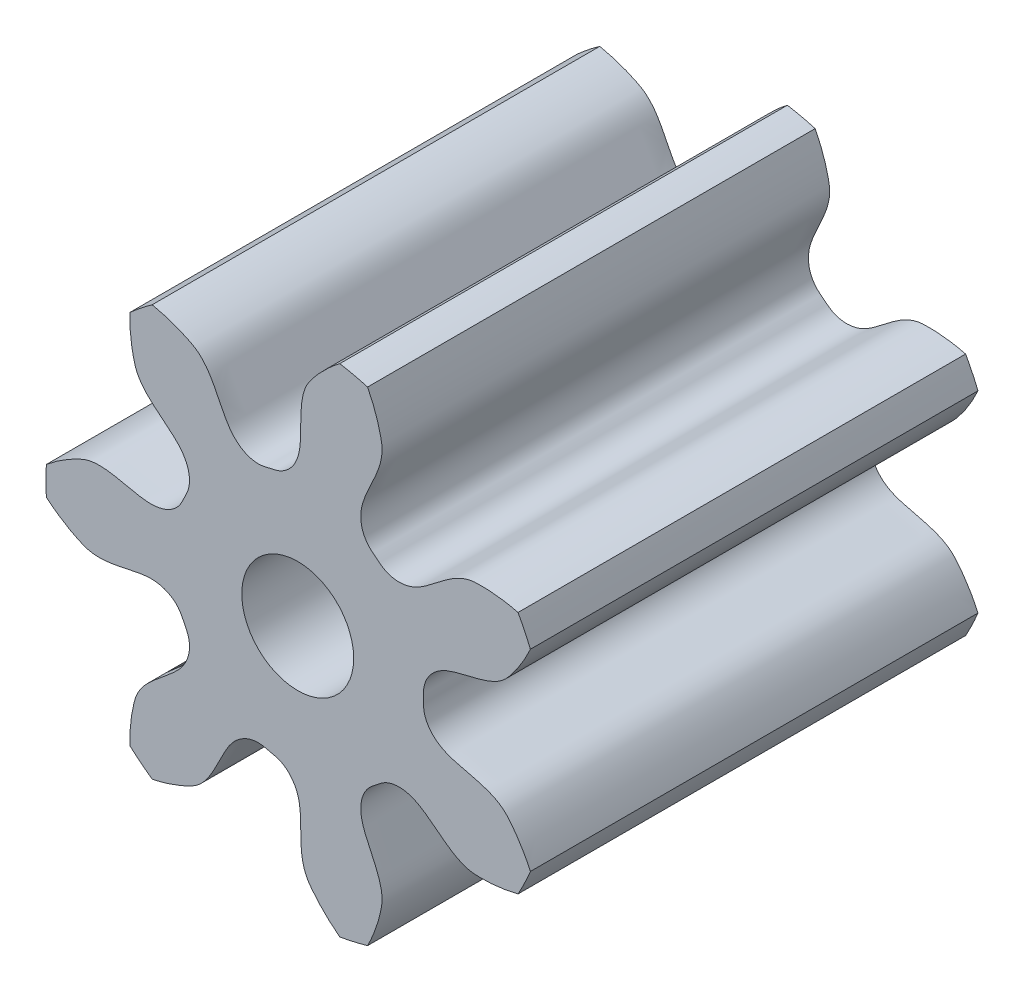
SolidWorks part; units mm, degrees
ref_plane "Front Plane" through (0, 0, 0) normal (0, 0, 1) x (1, 0, 0)
ref_plane "Top Plane" through (0, 0, 0) normal (0, 1, 0) x (1, 0, 0)
ref_plane "Right Plane" through (0, 0, 0) normal (1, 0, 0) x (0, 0, -1)
ref_axis "Axis1" through (0, 0, 55) along (0, 0, -1)
sketch "SketchRevolveSpurGear2" plane through (0, 0, 0) normal (1, 0, 0) x (0, 0, -1)
  line L0 (0, 0) -> (1, 0) construction
  line L1 (-9.525, 0) -> (-9.525, 2.25)
  line L2 (-9.525, 2.25) -> (9.525, 2.25)
  line L3 (9.525, 2.25) -> (9.525, 0)
  line L4 (9.525, 0) -> (-9.525, 0)
  dimension "Side1" = 9.525
  dimension "OutsideRadius" = 2.25
  dimension "Side2" = 9.525
revolve "SpurGear2" add sketch "SketchRevolveSpurGear2" angle 360 about L0
sketch "SketchToothSpurGear2" plane through (0, 0, 0) normal (0, 0, 1) x (1, 0, 0)
  arc A0 (2.0931, 0.8913) -> (2.0931, -0.8913) centre (0, 0) cw
  spline S0 degree 3 poles (2.0931, -0.8913) (2.0657, -0.8275) (2.0247, -0.7468) (1.9653, -0.6547) (1.9316, -0.6072) (1.8977, -0.5647) (1.7571, -0.3959) (1.5224, -0.3895) (1.348, -0.3264) (1.3443, -0.3251) (1.3407, -0.3237) (1.337, -0.3222) (1.3334, -0.3208) (1.3298, -0.3193) (1.3262, -0.3178) (1.3226, -0.3162) (1.3191, -0.3147) (1.3155, -0.3131) (1.312, -0.3114) (1.3085, -0.3098) (1.3051, -0.3081) (1.3016, -0.3064) (1.2982, -0.3046) (1.2948, -0.3029) (1.2914, -0.3011) (1.288, -0.2992) (1.2847, -0.2974) (1.2813, -0.2955) (1.278, -0.2935) (1.2748, -0.2916) (1.2715, -0.2896) (1.2682, -0.2876) (1.265, -0.2855) (1.2618, -0.2834) (1.2587, -0.2813) (1.2555, -0.2792) (1.2524, -0.277) (1.2493, -0.2748) (1.2462, -0.2726) (1.2432, -0.2703) (1.2401, -0.268) (1.2371, -0.2657) (1.2341, -0.2633) (1.2312, -0.2609) (1.2283, -0.2584) (1.2254, -0.256) (1.2225, -0.2535) (1.2196, -0.2509) (1.2168, -0.2484) (1.214, -0.2458) (1.2113, -0.2431) (1.2085, -0.2405) (1.2058, -0.2378) (1.2032, -0.235) (1.2005, -0.2322) (1.1979, -0.2294) (1.1953, -0.2266) (1.1928, -0.2237) (1.1903, -0.2208) (1.1878, -0.2179) (1.1854, -0.2149) (1.183, -0.2119) (1.1806, -0.2088) (1.1782, -0.2057) (1.176, -0.2026) (1.1737, -0.1994) (1.1715, -0.1962) (1.1693, -0.193) (1.1672, -0.1898) (1.1651, -0.1865) (1.163, -0.1831) (1.161, -0.1798) (1.159, -0.1764) (1.1571, -0.1729) (1.1552, -0.1695) (1.1534, -0.166) (1.1516, -0.1624) (1.1499, -0.1589) (1.1482, -0.1553) (1.1465, -0.1517) (1.1449, -0.148) (1.1434, -0.1443) (1.1419, -0.1406) (1.1405, -0.1369) (1.1391, -0.1331) (1.1378, -0.1293) (1.1365, -0.1255) (1.1353, -0.1217) (1.1342, -0.1178) (1.1331, -0.1139) (1.1321, -0.11) (1.1311, -0.106) (1.1302, -0.1021) (1.1293, -0.0981) (1.1286, -0.0941) (1.1278, -0.0901) (1.1272, -0.0861) (1.1266, -0.082) (1.1261, -0.078) (1.1256, -0.0739) (1.1252, -0.0698) (1.1249, -0.0658) (1.1246, -0.0617) (1.1244, -0.0576) (1.1243, -0.0535) (1.1242, -0.0494) (1.1242, -0.0452) (1.1243, -0.0417) (1.1247, -0.0266) (1.1253, 0) (1.1247, 0.0266) (1.1243, 0.0417) (1.1242, 0.0452) (1.1242, 0.0494) (1.1243, 0.0535) (1.1244, 0.0576) (1.1246, 0.0617) (1.1249, 0.0658) (1.1252, 0.0698) (1.1256, 0.0739) (1.1261, 0.078) (1.1266, 0.082) (1.1272, 0.0861) (1.1278, 0.0901) (1.1286, 0.0941) (1.1293, 0.0981) (1.1302, 0.1021) (1.1311, 0.106) (1.1321, 0.11) (1.1331, 0.1139) (1.1342, 0.1178) (1.1353, 0.1217) (1.1365, 0.1255) (1.1378, 0.1293) (1.1391, 0.1331) (1.1405, 0.1369) (1.1419, 0.1406) (1.1434, 0.1443) (1.1449, 0.148) (1.1465, 0.1517) (1.1482, 0.1553) (1.1499, 0.1589) (1.1516, 0.1624) (1.1534, 0.166) (1.1552, 0.1695) (1.1571, 0.1729) (1.159, 0.1764) (1.161, 0.1798) (1.163, 0.1831) (1.1651, 0.1865) (1.1672, 0.1898) (1.1693, 0.193) (1.1715, 0.1962) (1.1737, 0.1994) (1.176, 0.2026) (1.1782, 0.2057) (1.1806, 0.2088) (1.183, 0.2119) (1.1854, 0.2149) (1.1878, 0.2179) (1.1903, 0.2208) (1.1928, 0.2237) (1.1953, 0.2266) (1.1979, 0.2294) (1.2005, 0.2322) (1.2032, 0.235) (1.2058, 0.2378) (1.2085, 0.2405) (1.2113, 0.2431) (1.214, 0.2458) (1.2168, 0.2484) (1.2196, 0.2509) (1.2225, 0.2535) (1.2254, 0.256) (1.2283, 0.2584) (1.2312, 0.2609) (1.2341, 0.2633) (1.2371, 0.2657) (1.2401, 0.268) (1.2432, 0.2703) (1.2462, 0.2726) (1.2493, 0.2748) (1.2524, 0.277) (1.2555, 0.2792) (1.2587, 0.2813) (1.2618, 0.2834) (1.265, 0.2855) (1.2682, 0.2876) (1.2715, 0.2896) (1.2748, 0.2916) (1.278, 0.2935) (1.2813, 0.2955) (1.2847, 0.2974) (1.288, 0.2992) (1.2914, 0.3011) (1.2948, 0.3029) (1.2982, 0.3046) (1.3016, 0.3064) (1.3051, 0.3081) (1.3085, 0.3098) (1.312, 0.3114) (1.3155, 0.3131) (1.3191, 0.3147) (1.3226, 0.3162) (1.3262, 0.3178) (1.3298, 0.3193) (1.3334, 0.3208) (1.337, 0.3222) (1.3407, 0.3237) (1.3443, 0.3251) (1.348, 0.3264) (1.5224, 0.3895) (1.7571, 0.3959) (1.8977, 0.5647) (1.9316, 0.6072) (1.9653, 0.6547) (2.0247, 0.7468) (2.0657, 0.8275) (2.0931, 0.8913) knots 0 0 0 0 0.07365 0.09555 0.116123 0.135368 0.153286 0.347093 0.348484 0.349873 0.351259 0.352643 0.354024 0.355402 0.356779 0.358153 0.359525 0.360894 0.362262 0.363628 0.364991 0.366353 0.367714 0.369072 0.370429 0.371785 0.373139 0.374492 0.375844 0.377194 0.378544 0.379893 0.38124 0.382587 0.383934 0.38528 0.386625 0.38797 0.389315 0.390659 0.392004 0.393348 0.394693 0.396038 0.397383 0.398728 0.400074 0.40142 0.402767 0.404115 0.405464 0.406814 0.408165 0.409516 0.410869 0.412224 0.41358 0.414937 0.416296 0.417656 0.419018 0.420382 0.421747 0.423115 0.424485 0.425856 0.42723 0.428606 0.429984 0.431364 0.432747 0.434132 0.43552 0.436909 0.438302 0.439696 0.441093 0.442493 0.443895 0.4453 0.446707 0.448117 0.449529 0.450943 0.45236 0.453779 0.455201 0.456625 0.458051 0.459479 0.460909 0.462342 0.463776 0.465213 0.466651 0.468091 0.469532 0.470975 0.472419 0.473865 0.475312 0.47676 0.478209 0.479659 0.481109 0.482561 0.484012 0.485464 0.486331 0.5 0.513669 0.514536 0.515988 0.517439 0.518891 0.520341 0.521791 0.52324 0.524688 0.526135 0.527581 0.529025 0.530468 0.531909 0.533349 0.534787 0.536224 0.537658 0.539091 0.540521 0.541949 0.543375 0.544799 0.546221 0.54764 0.549057 0.550471 0.551883 0.553293 0.5547 0.556105 0.557507 0.558907 0.560304 0.561698 0.563091 0.56448 0.565868 0.567253 0.568636 0.570016 0.571394 0.57277 0.574144 0.575515 0.576885 0.578253 0.579618 0.580982 0.582344 0.583704 0.585063 0.58642 0.587776 0.589131 0.590484 0.591835 0.593186 0.594536 0.595885 0.597233 0.59858 0.599926 0.601272 0.602617 0.603962 0.605307 0.606652 0.607996 0.609341 0.610685 0.61203 0.613375 0.61472 0.616066 0.617413 0.61876 0.620107 0.621456 0.622806 0.624156 0.625508 0.626861 0.628215 0.629571 0.630928 0.632286 0.633647 0.635009 0.636372 0.637738 0.639106 0.640475 0.641847 0.643221 0.644598 0.645976 0.647357 0.648741 0.650127 0.651516 0.652907 0.846714 0.864632 0.883877 0.90445 0.92635 1 1 1 1
extrude "ToothExtrudeCutSpurGear2" cut sketch "SketchToothSpurGear2" against normal blind 9.525 and the other way blind 9.525
pattern_circular "PatternSpurGear2" count 7 every 51.429 about axis through (0, 0, 55) along (0, 0, -1) of "ToothExtrudeCutSpurGear2"
sketch "BoreRevolveSketch" plane through (0, 0, 0) normal (1, 0, 0) x (0, 0, -1)
  line L0 (0, 0) -> (1, 0) construction
  line L1 (-9.525, 0) -> (9.525, 0)
  line L2 (9.525, 0) -> (9.525, 6.35)
  line L3 (9.525, 6.35) -> (-9.525, 6.35)
  line L4 (-9.525, 6.35) -> (-9.525, 0)
  dimension "BoreSide1" = 9.525
  dimension "TaperSide1" = 6.35
  dimension "BoreSide2" = 9.525
  dimension "TaperSide2" = 6.35
sketch "AuxiliarySketchSpurGear2" plane through (0, 0, 0) normal (0, 0, 1) x (1, 0, 0)
  circle A0 centre (0, 0) radius 1.75 construction
  circle A1 centre (0, 0) radius 1.6445 construction
  circle A2 centre (0, 0) radius 1.8943 construction
  circle A3 centre (0, 0) radius 2.25 construction
  circle A4 centre (0, 0) radius 1.125 construction
  dimension "PitchDiameter" = 3.5
  dimension "BaseDiameter" = 3.2889
  dimension "FormDiameter" = 3.7886
  dimension "MajorDiameter" = 4.5
  dimension "MinorDiameter" = 2.25
sketch "Sketch2" plane through (0, 0, 9.525) normal (0, 0, 1) x (1, 0, 0)
  circle A0 centre (0, 0) radius 2.25
extrude "Cut-Extrude1" cut sketch "Sketch2" against normal blind 15.05
sketch "Sketch3" plane through (0, 0, -5.525) normal (0, 0, 1) x (1, 0, 0)
  circle A0 centre (0, 0) radius 0.5
  dimension "D1" = 1
extrude "Cut-Extrude2" cut sketch "Sketch3" against normal blind 15.05
